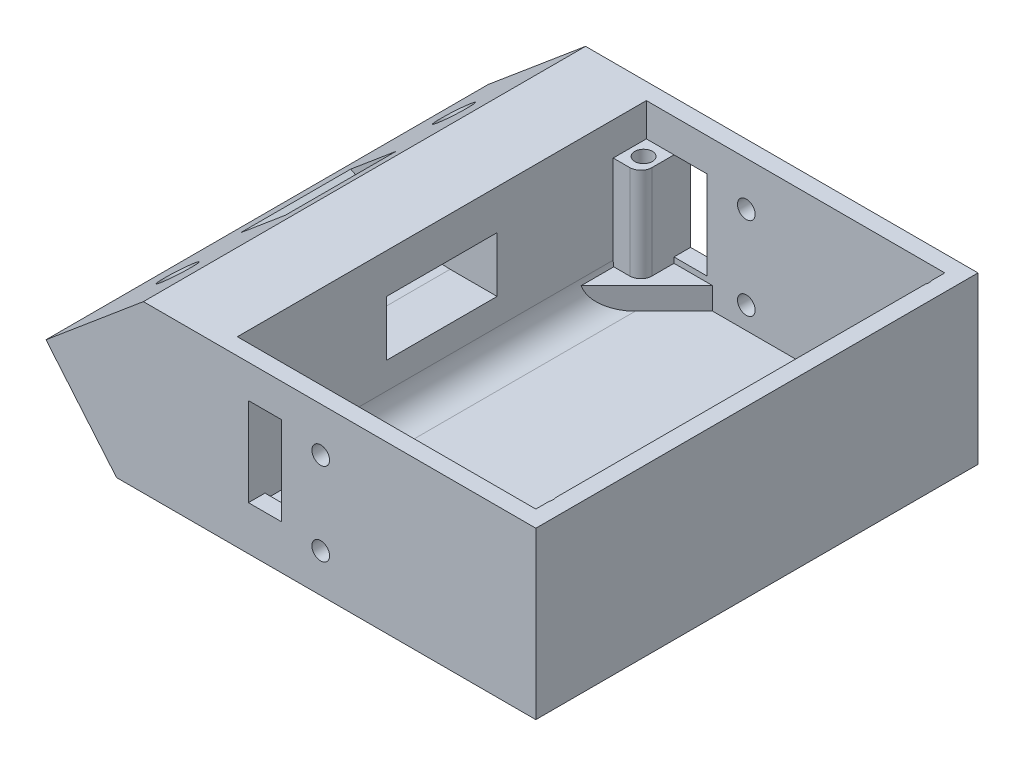
SolidWorks part; units mm, degrees
ref_plane "Спереди" through (0, 0, 0) normal (0, 0, 1) x (1, 0, 0)
ref_plane "Сверху" through (0, 0, 0) normal (0, 1, 0) x (1, 0, 0)
ref_plane "Справа" through (0, 0, 0) normal (1, 0, 0) x (0, 0, -1)
sketch "Sketch1" plane through (0, 0, 0) normal (0, 1, 0) x (1, 0, 0)
  line L1 (30.5, -40) -> (-30.5, -40)
  line L2 (30.5, -40) -> (30.5, 40)
  line L3 (30.5, 40) -> (-30.5, 40)
  line L4 (-30.5, -40) -> (-30.5, 40)
  line L5 (30.5, -40) -> (-30.5, 40) construction
  line L6 (30.5, 40) -> (-30.5, -40) construction
  point P0 (0, 0)
  dimension "D1" = 80
  dimension "D2" = 61
extrude "Boss-Extrude1" add sketch "Sketch1" along normal blind 30
sketch "Sketch2" plane through (0, 30, 0) normal (0, 1, 0) x (1, 0, 0)
  line L0 (30.5, 40) -> (-30.5, 40) construction
  line L1 (-26.5, -37) -> (27.5, -37)
  line L2 (-26.5, -37) -> (-26.5, 37)
  line L3 (-26.5, 37) -> (27.5, 37)
  line L4 (27.5, -37) -> (27.5, 37)
  line L5 (-30.5, -40) -> (30.5, -40) construction
  line L6 (-30.5, 40) -> (-30.5, -40) construction
  line L7 (30.5, -40) -> (30.5, 40) construction
  point P0 (0, 0)
  dimension "D1" = 3
  dimension "D2" = 3
  dimension "D3" = 3
  dimension "D4" = 4
extrude "Cut-Extrude1" cut sketch "Sketch2" against normal blind 27
sketch "Sketch11" plane through (0, 0, 40) normal (0, 0, 1) x (1, 0, 0)
  line L0 (-30.5, 30) -> (-40.5, 30)
  line L1 (-30.5, 0) -> (-58.119, 0)
  line L2 (-30.5, 0) -> (-30.5, 30)
  line L3 (-58.119, 0) -> (-58.119, 15.2159)
  line L4 (-40.5, 30) -> (-58.119, 15.2159)
  line L5 (-40.5, 30) -> (-40.5, 0) construction
  dimension "D1" = 23
  dimension "D2" = 50
  dimension "D3" = 10
extrude "Boss-Extrude3" add sketch "Sketch11" against normal up to surface (80 mm away) up to face at (0, 15, -40)
sketch "Sketch7" plane through (0, 3, 0) normal (0, 1, 0) x (1, 0, 0)
  line L0 (27.5, -25) -> (15.5, -37)
  line L1 (27.5, -37) -> (27.5, 37) construction
  line L2 (-26.5, -37) -> (27.5, -37) construction
  line L3 (15.5, -37) -> (27.5, -37)
  line L4 (27.5, -37) -> (27.5, -25)
  line L5 (27.5, 25) -> (15.5, 37)
  line L6 (27.5, 37) -> (-26.5, 37) construction
  line L7 (15.5, 37) -> (27.5, 37)
  line L8 (27.5, 37) -> (27.5, 25)
  line L9 (-26.5, 25) -> (-14.5, 37)
  line L10 (-26.5, 37) -> (-26.5, -37) construction
  line L11 (-14.5, 37) -> (-26.5, 37)
  line L12 (-26.5, 37) -> (-26.5, 25)
  line L13 (-14.5, -37) -> (-26.5, -25)
  line L14 (-26.5, 37) -> (-26.5, -37) construction
  line L15 (-26.5, -25) -> (-26.5, -37)
  line L16 (-26.5, -37) -> (-14.5, -37)
  dimension "D1" = 12
extrude "Boss-Extrude2" add sketch "Sketch7" along normal blind 4
sketch "Sketch5" plane through (0, 0, 0) normal (0, -1, 0) x (1, 0, 0)
  line L0 (1, -40) -> (1, 40) construction
  line L1 (30.5, -40) -> (-58.119, -40) construction
  line L2 (-58.119, 40) -> (30.5, 40) construction
  line L4 (26, 34) -> (-24, 34) construction
  line L5 (26, 34) -> (26, -34) construction
  line L6 (26, -34) -> (-24, -34) construction
  line L7 (-24, 34) -> (-24, -34) construction
  line L8 (26, 34) -> (-24, -34) construction
  line L9 (26, -34) -> (-24, 34) construction
  circle A0 centre (-24, -34) radius 1.6
  circle A1 centre (-24, 34) radius 1.6
  circle A2 centre (26, 34) radius 1.6
  circle A3 centre (26, -34) radius 1.6
  point P6 (1, 0)
  dimension "D4" = 3.2
  dimension "D1" = 68
  dimension "D2" = 50
  dimension "D3" = 1
extrude "Cut-Extrude3" cut sketch "Sketch5" against normal through all
sketch "Sketch8" plane through (0, 0, 0) normal (0, -1, 0) x (1, 0, 0)
  line L0 (30.5, -40) -> (-58.119, -40) construction
  line L1 (-25.625, 36.8146) -> (-27.25, 34)
  line L2 (-27.25, 34) -> (-25.625, 31.1854)
  line L3 (-25.625, 31.1854) -> (-22.375, 31.1854)
  line L4 (-22.375, 31.1854) -> (-20.75, 34)
  line L5 (-20.75, 34) -> (-22.375, 36.8146)
  line L6 (-22.375, 36.8146) -> (-25.625, 36.8146)
  line L7 (24.375, 36.8146) -> (22.75, 34)
  line L8 (22.75, 34) -> (24.375, 31.1854)
  line L9 (24.375, 31.1854) -> (27.625, 31.1854)
  line L10 (27.625, 31.1854) -> (29.25, 34)
  line L11 (29.25, 34) -> (27.625, 36.8146)
  line L12 (27.625, 36.8146) -> (24.375, 36.8146)
  line L13 (-25.625, -31.1854) -> (-27.25, -34)
  line L14 (-27.25, -34) -> (-25.625, -36.8146)
  line L15 (-25.625, -36.8146) -> (-22.375, -36.8146)
  line L16 (-22.375, -36.8146) -> (-20.75, -34)
  line L17 (-20.75, -34) -> (-22.375, -31.1854)
  line L18 (-22.375, -31.1854) -> (-25.625, -31.1854)
  line L19 (24.375, -31.1854) -> (22.75, -34)
  line L20 (22.75, -34) -> (24.375, -36.8146)
  line L21 (24.375, -36.8146) -> (27.625, -36.8146)
  line L22 (27.625, -36.8146) -> (29.25, -34)
  line L23 (29.25, -34) -> (27.625, -31.1854)
  line L24 (27.625, -31.1854) -> (24.375, -31.1854)
  circle A0 centre (-24, 34) radius 3.25 construction
  circle A1 centre (26, 34) radius 3.25 construction
  circle A2 centre (-24, -34) radius 3.25 construction
  circle A3 centre (26, -34) radius 3.25 construction
  dimension "D1" = 6.5
extrude "Cut-Extrude4" cut sketch "Sketch8" against normal blind 3
sketch "Sketch12" plane through (0, 0, 40) normal (0, 0, 1) x (1, 0, 0)
  line L0 (-58.119, 15.2159) -> (-45.3514, 0)
  line L1 (-58.119, 0) -> (30.5, 0) construction
  line L2 (-45.3514, 0) -> (-58.119, 0)
  line L3 (-58.119, 0) -> (-58.119, 15.2159)
  line L4 (-40.5, 30) -> (-58.119, 15.2159) construction
extrude "Cut-Extrude6" cut sketch "Sketch12" against normal through all
sketch "Sketch16" plane through (-31.5057, 37.5471, 0) normal (-0.6428, 0.766, 0) x (0.766, 0.6428, 0)
  line L0 (-23.2412, 40) -> (-23.2412, -40) construction
  line L1 (-34.7412, 40) -> (-11.7412, 40) construction
  line L2 (-11.7412, -40) -> (-34.7412, -40) construction
  circle A0 centre (-23.2412, 25) radius 3.1
  circle A1 centre (-23.2412, -25) radius 3.1
  point P10 (-23.2412, 0)
  dimension "D1" = 6.2
  dimension "D2" = 50
  dimension "D3" = 25
extrude "Cut-Extrude8" cut sketch "Sketch16" against normal through all
fillet "Fillet1" radius 5 1 edges at (-26.5, 3, 0)
sketch "Sketch17" plane through (-31.5057, 37.5471, 0) normal (-0.6428, 0.766, 0) x (0.766, 0.6428, 0)
  circle A0 centre (-23.2412, -25) radius 6.5
  circle A1 centre (-23.2412, 25) radius 6.5
  dimension "D2" = 13
extrude "Cut-Extrude9" cut sketch "Sketch17" against normal blind 10 from offset 25 offset against normal yes
sketch "Sketch18" plane through (0, 0, 40) normal (0, 0, 1) x (1, 0, 0)
  line L0 (-44.8128, 26.3811) -> (-37.8032, 22.8149)
  line L2 (-40.5, 30) -> (-58.119, 15.2159) construction
  line L3 (-37.8032, 22.8149) -> (-23.8032, 22.8149)
  line L4 (-23.8032, 22.8149) -> (-23.8032, 12.8149)
  line L5 (-23.8032, 12.8149) -> (-39.8032, 12.8149)
  line L6 (-39.8032, 12.8149) -> (-52.9869, 19.5222)
  line L7 (-52.9869, 19.5222) -> (-44.8128, 26.3811)
  dimension "D1" = 10
  dimension "D2" = 14
  dimension "D3" = 16
extrude "Cut-Extrude10" cut sketch "Sketch18" against normal blind 20 from offset 30 offset against normal yes
fillet "Fillet2" radius 20 2 edges at (-39.8032, 12.8149, 0) (-37.8032, 22.8149, 0)
sketch "Sketch19" plane through (0, 0, 40) normal (0, 0, 1) x (1, 0, 0)
  line L0 (-45.3514, 0) -> (-8.4162, 0) construction
  line L1 (-45.3514, 0) -> (30.5, 0) construction
  line L2 (-8.4162, -0.4537) -> (-8.4162, 30) construction
  line L3 (-40.5, 30) -> (30.5, 30) construction
  circle A0 centre (-8.4162, 22) radius 1.6
  circle A1 centre (-8.4162, 7) radius 1.6
  dimension "D2" = 3.2
  dimension "D3" = 15
  dimension "D1" = 36.9352
  dimension "D4" = 8
extrude "Cut-Extrude11" cut sketch "Sketch19" against normal through all
sketch "Sketch20" plane through (0, 0, 37) normal (0, 0, -1) x (-1, 0, 0)
  line L0 (21.5, 8) -> (21.5, 24)
  line L2 (21.5, 24) -> (15.5, 24)
  line L3 (15.5, 24) -> (15.5, 8)
  line L4 (15.5, 8) -> (21.5, 8)
  line L5 (40.5, 30) -> (-30.5, 30) construction
  line L6 (26.5, 8) -> (26.5, 30) construction
  line L7 (26.5, 8) -> (-6.3924, 8) construction
  dimension "D1" = 6
  dimension "D2" = 6
  dimension "D3" = 5
extrude "Cut-Extrude12" cut sketch "Sketch20" along normal through all both and the other way through all
sketch "Sketch21" plane through (0, 7, 0) normal (0, 1, 0) x (1, 0, 0)
  line L0 (-26.5, -37) -> (-26.5, 37) construction
  line L1 (-21.5, -31) -> (-26.5, -31)
  line L2 (-21.5, -31) -> (-21.5, -37)
  line L3 (-21.5, -37) -> (-26.5, -37)
  line L4 (-26.5, -31) -> (-26.5, -37)
  line L5 (-21.5, -31) -> (-26.5, -37) construction
  line L6 (-21.5, -37) -> (-26.5, -31) construction
  line L7 (-26.399, -37) -> (-14.5, -37) construction
  line L8 (-14.5, 37) -> (-26.399, 37) construction
  line L9 (-26.5, 31) -> (-21.5, 31)
  line L10 (-26.5, 31) -> (-26.5, 37)
  line L11 (-26.5, 37) -> (-21.5, 37)
  line L12 (-21.5, 31) -> (-21.5, 37)
  line L13 (-26.5, 31) -> (-21.5, 37) construction
  line L14 (-26.5, 37) -> (-21.5, 31) construction
  line L15 (27.5, 37) -> (15.5, 37) construction
  line L16 (29, 31) -> (23, 31)
  line L17 (29, 31) -> (29, 37)
  line L18 (29, 37) -> (23, 37)
  line L19 (23, 31) -> (23, 37)
  line L20 (29, 31) -> (23, 37) construction
  line L21 (29, 37) -> (23, 31) construction
  line L22 (15.5, -37) -> (27.5, -37) construction
  line L23 (29, -31) -> (23, -31)
  line L24 (29, -31) -> (29, -37)
  line L25 (29, -37) -> (23, -37)
  line L26 (23, -31) -> (23, -37)
  line L27 (29, -31) -> (23, -37) construction
  line L28 (29, -37) -> (23, -31) construction
  circle A0 centre (-24, -34) radius 1.6
  circle A1 centre (-24, -34) radius 1.6 construction
  circle A2 centre (-24, 34) radius 1.6
  circle A3 centre (-24, 34) radius 1.6 construction
  circle A4 centre (26, 34) radius 1.6
  arc A5 (27.5, 34.5568) -> (27.5, 33.4432) centre (26, 34) ccw construction
  circle A6 centre (26, -34) radius 1.6
  arc A7 (27.5, -33.4432) -> (27.5, -34.5568) centre (26, -34) ccw construction
  point P0 (-24, -34)
  point P14 (-24, 34)
  point P26 (26, 34)
  point P39 (26, -34)
  dimension "D1" = 6
extrude "Boss-Extrude4" add sketch "Sketch21" along normal up to surface (17 mm away) up to face at (-18.5, 24, 38.5)
fillet "Fillet4" radius 2 4 edges at (23, 15.5, -31) (23, 15.5, 31) (-21.5, 15.5, 31) (-21.5, 15.5, -31)
